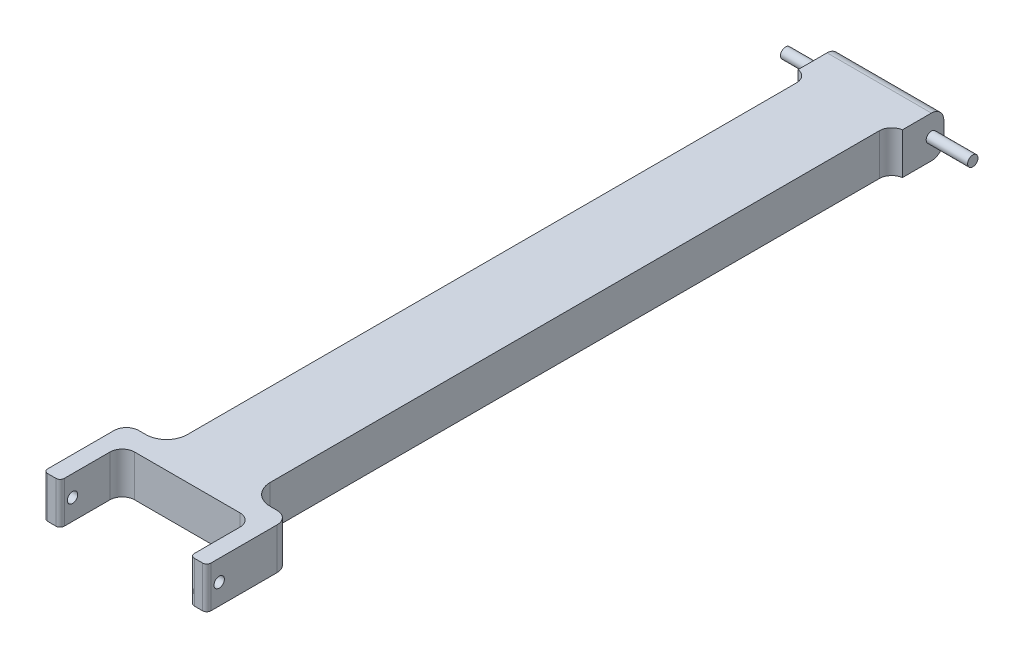
SolidWorks part; units mm, degrees
ref_plane "Front Plane" through (0, 0, 0) normal (0, 0, 1) x (1, 0, 0)
ref_plane "Top Plane" through (0, 0, 0) normal (0, 1, 0) x (1, 0, 0)
ref_plane "Right Plane" through (0, 0, 0) normal (1, 0, 0) x (0, 0, -1)
sketch "Sketch1" plane through (0, 0, 0) normal (0, 0, 1) x (1, 0, 0)
  line L1 (0, 0) -> (39.39, 0)
  line L2 (0, 0) -> (0, 10)
  line L3 (0, 10) -> (39.39, 10)
  line L4 (39.39, 0) -> (39.39, 10)
  dimension "D1" = 39.39
  dimension "D2" = 10
extrude "Boss-Extrude1" add sketch "Sketch1" along normal blind 20
sketch "Sketch2" plane through (0, 0, 20) normal (0, 0, 1) x (1, 0, 0)
  line L0 (0, 0) -> (39.39, 0) construction
  line L1 (4, 0) -> (35.39, 0)
  line L2 (4, 0) -> (4, 10)
  line L3 (4, 10) -> (35.39, 10)
  line L4 (35.39, 0) -> (35.39, 10)
  line L5 (39.39, 10) -> (0, 10) construction
  line L6 (0, 5) -> (4, 5) construction
  line L7 (39.39, 0) -> (39.39, 10) construction
  line L8 (0, 10) -> (0, 0) construction
  line L9 (35.39, 5) -> (39.39, 5) construction
  dimension "D1" = 31.39
extrude "Cut-Extrude1" cut sketch "Sketch2" against normal blind 15
sketch "Sketch3" plane through (0, 0, 0) normal (-1, 0, 0) x (0, 0, 1)
  line L0 (20, 5) -> (0, 5) construction
  line L1 (20, 10) -> (20, 0) construction
  line L2 (0, 10) -> (0, 0) construction
  line L3 (17, 0) -> (17, 10) construction
  line L4 (20, 0) -> (0, 0) construction
  line L5 (20, 10) -> (0, 10) construction
  circle A0 centre (17, 5) radius 1.25
  point P15 (17, 5)
  dimension "D1" = 2.5
extrude "Cut-Extrude2" cut sketch "Sketch3" against normal through all both and the other way through all
fillet "Fillet1" radius 3 4 edges at (39.39, 5, 0) (0, 5, 0) (4, 5, 5) (35.39, 5, 5)
fillet "Fillet3" radius 1 4 edges at (0, 5, 20) (4, 5, 20) (35.39, 5, 20) (39.39, 5, 20)
sketch "Sketch4" plane through (0, 0, 0) normal (0, 0, -1) x (-1, 0, 0)
  line L0 (-36.39, 10) -> (-3, 10) construction
  line L1 (-29.695, 10) -> (-9.695, 10)
  line L2 (-29.695, 10) -> (-29.695, 0)
  line L3 (-29.695, 0) -> (-9.695, 0)
  line L4 (-9.695, 10) -> (-9.695, 0)
  line L5 (-3, 0) -> (-36.39, 0) construction
  line L6 (-3, 5) -> (-9.695, 5) construction
  line L7 (-3, 0) -> (-3, 10) construction
  line L8 (-36.39, 5) -> (-29.695, 5) construction
  line L9 (-36.39, 10) -> (-36.39, 0) construction
  point P8 (-29.695, 5)
  dimension "D1" = 20
extrude "Boss-Extrude2" add sketch "Sketch4" along normal blind 165
fillet "Fillet4" radius 5 2 edges at (9.695, 5, 0) (29.695, 5, 0)
sketch "Sketch7" plane through (9.695, 0, 0) normal (-1, 0, 0) x (0, 0, 1)
  line L0 (-165, 10) -> (-5, 10) construction
  line L1 (-165, 0) -> (-155, 0)
  line L2 (-165, 0) -> (-165, 10)
  line L3 (-165, 10) -> (-155, 10)
  line L4 (-155, 0) -> (-155, 10)
  dimension "D1" = 10
extrude "Boss-Extrude5" add sketch "Sketch7" along normal blind 2.59
sketch "Sketch8" plane through (29.695, 0, 0) normal (1, 0, 0) x (0, 0, -1)
  line L0 (165, 0) -> (5, 0) construction
  line L1 (165, 10) -> (155, 10)
  line L2 (165, 10) -> (165, 0)
  line L3 (165, 0) -> (155, 0)
  line L4 (155, 10) -> (155, 0)
  dimension "D1" = 10
extrude "Boss-Extrude6" add sketch "Sketch8" along normal blind 2.59
fillet "Fillet7" radius 3 2 edges at (9.695, 5, -155) (29.695, 5, -155)
fillet "Fillet11" radius 3 2 edges at (19.695, 10, -165) (19.695, 0, -165)
sketch "Sketch9" plane through (7.105, 0, 0) normal (-1, 0, 0) x (0, 0, 1)
  line L0 (-165, 5) -> (-155, 5) construction
  line L1 (-165, 7) -> (-165, 3) construction
  line L2 (-155, 0) -> (-155, 10) construction
  line L3 (-162, 0) -> (-162, 10) construction
  circle A0 centre (-162, 5) radius 1.25
  dimension "D1" = 2.5
extrude "Boss-Extrude7" add sketch "Sketch9" along normal blind 10
sketch "Sketch10" plane through (32.285, 0, 0) normal (1, 0, 0) x (0, 0, -1)
  line L0 (165, 5) -> (155, 5) construction
  line L1 (165, 3) -> (165, 7) construction
  line L2 (155, 10) -> (155, 0) construction
  line L3 (162, 10) -> (162, 0) construction
  circle A0 centre (162, 5) radius 1.25
  dimension "D1" = 2.5
extrude "Boss-Extrude8" add sketch "Sketch10" along normal blind 10
